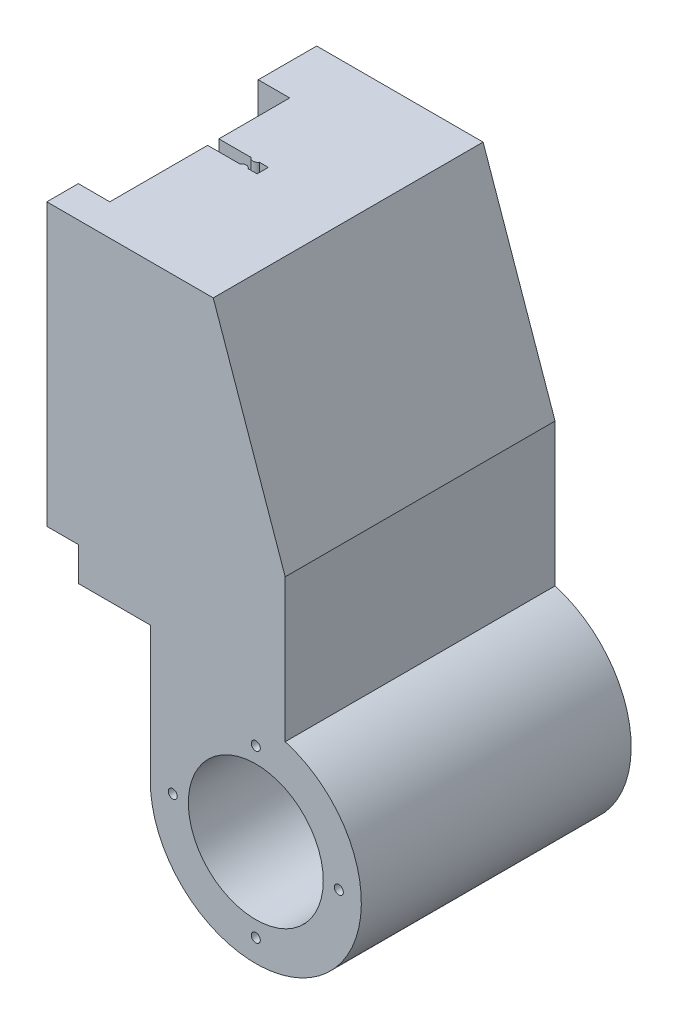
SolidWorks part; units mm, degrees
ref_plane "Front Plane" through (0, 0, 0) normal (0, 0, 1) x (1, 0, 0)
ref_plane "Top Plane" through (0, 0, 0) normal (0, 1, 0) x (1, 0, 0)
ref_plane "Right Plane" through (0, 0, 0) normal (1, 0, 0) x (0, 0, -1)
sketch "Sketch1" plane through (0, 0, 0.7555) normal (0, 0, 1) x (1, 0, 0)
  line L0 (-30.8511, 11.3225) -> (-30.8511, 7.8225)
  line L1 (-37.1011, 17.5725) -> (-40.6011, 17.5725)
  line L2 (-30.8511, 27.3225) -> (-30.8511, 23.8225)
  line L3 (-24.6011, 17.5725) -> (-21.1011, 17.5725)
  circle A2 centre (-30.8511, 9.5725) radius 0.75
  circle A3 centre (-38.8511, 17.5725) radius 0.75
  circle A4 centre (-30.8511, 25.5725) radius 0.75
  circle A5 centre (-22.8511, 17.5725) radius 0.75
  circle A6 centre (-30.8511, 17.5725) radius 16
  circle A7 centre (-30.8511, 17.5725) radius 5.3
  line M1 (-24.957, 26.8601) -> (-29.1868, 25.0317)
  line M2 (-29.1868, 25.0317) -> (-28.1663, 21.9086)
  line M3 (-28.1663, 21.9086) -> (-24.957, 26.8601)
  dimension "D1" = 32
  dimension "D2" = 10.6
  dimension "D3" = 1.5
  dimension "D4" = 1.5
  dimension "D5" = 1.5
  dimension "D6" = 1.5
extrude "Boss-Extrude1" add sketch "Sketch1" along normal blind 60 contours A6 A7 A2 A3 A4 A5 M2 M1 M3 | A7 M3 M1 M2 | A7 M2 M3 | L1 A3 | L1 A3 | L0 A2 | L0 A2 | L3 A5 | L3 A5 | L2 A4 | L2 A4 region at (-30.5328, 9.5725, 0.7555) region at (-31.1694, 9.5725, 0.7555) region at (-38.8511, 17.2542, 0.7555) region at (-38.8511, 17.8908, 0.7555) region at (-30.5328, 25.5725, 0.7555) region at (-31.1694, 25.5725, 0.7555) region at (-22.8511, 17.8908, 0.7555) region at (-22.8511, 17.2542, 0.7555) region at (-46.3986, 17.5725, 0.7555) region at (-30.8518, 17.5713, 0.7555) region at (-27.4344, 24.6082, 0.7555)
sketch "Sketch2" plane through (0, 0, 60.7555) normal (0, 0, 1) x (1, 0, 0)
  line L0 (-46.8511, 17.5725) -> (-46.8511, 117.5725)
  line L1 (-46.8511, 117.5725) -> (-14.8511, 117.5725)
  line L2 (-14.8511, 117.5725) -> (-14.8511, 17.5725)
  line L3 (-30.8511, 17.5725) -> (-60.8511, 17.5725)
  line L4 (-60.8511, 57.5725) -> (-60.8511, 117.5725)
  line L5 (-60.8511, 117.5725) -> (-46.8511, 117.5725)
  line L7 (-30.8511, 117.5725) -> (-14.8511, 71.8582)
  line L8 (-60.8511, 57.5725) -> (-60.8511, 17.5725)
  circle A0 centre (-30.8511, 17.5725) radius 16 construction
  circle M7 centre (-30.8511, 17.5725) radius 16
  dimension "D1" = 100
  dimension "D2" = 30
  dimension "D3" = 100
  dimension "D4" = 60
extrude "Boss-Extrude2" add sketch "Sketch2" against normal blind 60 contours L7 L1 L0 L2 M7 | L4 L0 L5 region at (-53.8511, 67.5725, 60.7555) region at (-32.455, 69.4896, 60.7555)
sketch "Sketch3" plane through (0, 117.5725, 0) normal (0, 1, 0) x (1, 0, 0)
  line L0 (-60.8511, -0.7555) -> (-60.8511, -28.7555)
  line L1 (-60.8511, -0.7555) -> (-60.8511, -60.7555) construction
  line L2 (-60.8511, -60.7555) -> (-60.8511, -32.7555)
  line L3 (-30.8511, -0.7555) -> (-30.8511, -29.5055)
  line L4 (-30.8511, -0.7555) -> (-30.8511, -60.7555) construction
  line L5 (-30.8511, -60.7555) -> (-30.8511, -32.0055)
  line L6 (-60.8511, -0.7555) -> (-49.8511, -0.7555)
  line L7 (-60.8511, -0.7555) -> (-30.8511, -0.7555) construction
  line L8 (-60.8511, -0.7555) -> (-58.8511, -0.7555)
  line L9 (-58.8511, -0.7555) -> (-58.8511, -60.7555)
  line L10 (-60.8511, -60.7555) -> (-30.8511, -60.7555) construction
  line L11 (-49.8511, -0.7555) -> (-49.8511, -60.7555)
  line L12 (-30.8511, -29.5055) -> (-58.8511, -29.5055)
  line L13 (-30.8511, -32.0055) -> (-58.8511, -32.0055)
  line L14 (-58.8511, -30.7555) -> (-60.8511, -30.7555)
  line L15 (-59.8511, -31.5055) -> (-59.8511, -30.0055)
  line L16 (-49.8511, -30.7555) -> (-53.8511, -30.7555)
  line L17 (-59.7707, -32.5947) -> (-49.8511, -32.5947)
  line L18 (-59.7707, -28.9162) -> (-49.8511, -28.9162)
  line L19 (-53.8511, -28.9162) -> (-53.8511, -32.5947)
  line L20 (-58.8511, -29.5055) -> (-60.8511, -29.5055)
  line L21 (-60.8511, -0.7555) -> (-60.8511, -60.7555) construction
  line L22 (-58.8511, -32.0055) -> (-60.8511, -32.0055)
  arc A0 (-60.8511, -28.7555) -> (-58.8511, -29.5055) centre (-59.7707, -28.9162) ccw
  arc A1 (-60.8511, -32.7555) -> (-58.8511, -32.0055) centre (-59.7707, -32.5947) cw
  circle A2 centre (-52.7589, -32.5947) radius 1.0922
  circle A3 centre (-52.7589, -28.9162) radius 1.0922
  point P31 (-59.8511, -30.7555)
  point P46 (-53.8511, -30.7555)
  line M10 (-60.8511, -0.7555) -> (-60.8511, -60.7555)
  dimension "D7" = 2.1845
  dimension "D8" = 2.1845
  dimension "D1" = 4
  dimension "D2" = 2.5
  dimension "D3" = 11
  dimension "D4" = 2
  dimension "D5" = 1.5
  dimension "D6" = 4
extrude "Cut-Extrude1" cut sketch "Sketch3" against normal through all contours L13 L11 L12 L9 | A3 L12 L19 L16 L11 | A2 L13 L11 L16 L19 | A0 L15 L14 L9 | A0 L20 L14 L15 M10 | L22 A1 L15 L14 M10 | L15 A1 L9 L14 | L20 A0 | A1 L22 region at (-60.4035, 117.5725, 30.2566) region at (-59.7707, 117.5725, 29.7112) region at (-56.3511, 117.5725, 30.7555) region at (-59.3076, 117.5725, 30.3023) region at (-60.4035, 117.5725, 31.2543) region at (-51.7149, 117.5725, 30.1933) region at (-59.3076, 117.5725, 31.2087) region at (-51.7149, 117.5725, 31.3176) region at (-59.7707, 117.5725, 31.7997)
sketch "Sketch4" plane through (0, 117.5725, 0) normal (0, 1, 0) x (1, 0, 0)
  line L0 (-60.8511, -27.2555) -> (-44.8511, -0.7555)
  line L1 (-60.8511, -0.7555) -> (-60.8511, -29.5055) construction
  line L2 (-60.8511, -0.7555) -> (-30.8511, -0.7555) construction
  line L3 (-60.8511, -34.2555) -> (-44.8511, -60.7555)
  line L4 (-60.8511, -32.0055) -> (-60.8511, -60.7555) construction
  line L5 (-60.8511, -60.7555) -> (-30.8511, -60.7555) construction
  line L6 (-44.8511, -0.7555) -> (-60.8511, -0.7555)
  line L7 (-60.8511, -0.7555) -> (-60.8511, -27.2555)
  line L8 (-60.8511, -34.2555) -> (-60.8511, -60.7555)
  line L9 (-60.8511, -60.7555) -> (-44.8511, -60.7555)
  dimension "D1" = 16
  dimension "D2" = 26.5
  dimension "D3" = 26.5
  dimension "D4" = 16
extrude "Cut-Extrude2" cut sketch "Sketch4" against normal through all
sketch "Sketch5" plane through (0, 0, 0.7555) normal (0, 0, -1) x (-1, 0, 0)
  line L0 (30.8511, 17.5725) -> (30.8511, 47.5725)
  line L1 (30.8511, 47.5725) -> (84.8511, 47.5725)
  line L3 (44.8511, 9.8265) -> (44.8511, 47.5725)
  line L4 (44.8511, 9.8265) -> (44.8511, 117.5725) construction
  line L5 (44.8511, 9.8265) -> (84.8511, 9.8265)
  line L6 (84.8511, 9.8265) -> (84.8511, 47.5725)
  line M8 (44.8511, 9.8265) -> (44.8511, 117.5725)
  dimension "D1" = 30
  dimension "D2" = 40
extrude "Cut-Extrude5" cut sketch "Sketch5" against normal through all contours L5 L6 L1 M8 region at (-64.8511, 28.6995, 0.7555)
sketch "Sketch10" plane through (0, 0, 60.7555) normal (0, 0, 1) x (1, 0, 0)
  line L0 (-44.8511, 9.8265) -> (-44.8511, 47.5725) construction
  line L1 (-21.3871, 17.5725) -> (-56.3871, 17.5725)
  line L2 (-21.3871, 17.5725) -> (-21.3871, -17.4275)
  line L3 (-30.8511, 17.5725) -> (-21.3871, 17.5725)
  line L4 (-24.6011, 17.5725) -> (-21.1011, 17.5725) construction
  line L5 (-21.3871, 17.5725) -> (-2.9231, 17.5725)
  line L6 (-2.9231, 17.5725) -> (-2.9231, 19.3225)
  line L7 (-21.3871, 17.5725) -> (-6.3871, 17.5725)
  circle A0 centre (-21.3871, 17.5725) radius 23.464
  circle A1 centre (-2.9231, 17.5725) radius 1
  circle A2 centre (-21.3871, -0.8915) radius 1
  circle A3 centre (-39.8511, 17.5725) radius 1
  circle A4 centre (-21.3871, 36.0365) radius 1
  circle A5 centre (-21.3871, 17.5725) radius 35
  circle A6 centre (-21.3871, 17.5725) radius 15
  point P21 (-21.3871, 17.5725)
  line M2 (-44.8511, 47.5725) -> (-44.8511, 9.8265)
  arc M3 (-44.8511, 9.8265) -> (-14.8511, 17.5725) centre (-30.8511, 17.5725) ccw
  line M4 (-14.8511, 17.5725) -> (-14.8511, 71.8582)
  arc M8 (-28.2602, 22.1961) -> (-28.0575, 22.0765) centre (-30.8511, 17.5725) cw
  line M9 (-28.0575, 22.0765) -> (-28.1663, 21.9086)
  line M10 (-28.1663, 21.9086) -> (-28.2602, 22.1961)
  dimension "D4" = 2
  dimension "D8" = 30
  dimension "D1" = 9.464
  dimension "D2" = 18.464
  dimension "D3" = 1.75
  dimension "D6" = 35
  dimension "D7" = 15
  dimension "D5" = 4
extrude "Boss-Extrude3" add sketch "Sketch10" against normal up to surface (60 mm away) contours A2 L2 A0 M3 | A3 L1 A0 L2 M3 | L5 L2 M3 | A2 L2 A0 A1 M4 M3 | A3 L1 L5 A0 A4 M4 M10 M8 M9 | L1 A3 | L1 A3 | A4 | L5 A1 L6 | L6 A1 L5 | L2 A2 | L2 A2 | L5 A6 M4 | L2 A6 L5 M3 | A6 L2 M3 | L1 A6 L2 M3 | A6 A0 L1 A3 A4 M4 region at (-27.8512, 11.3508, 60.7555) region at (-18.7207, 12.5689, 60.7555) region at (-24.4076, 24.2518, 60.7555) region at (-13.1664, 10.5233, 60.7555) region at (-22.4089, 3.3164, 60.7555) region at (-11.3674, 22.9008, 60.7555) region at (-37.3564, 9.1245, 60.7555) region at (-31.0311, 31.187, 60.7555) region at (-3.3475, 17.9969, 60.7555) region at (-2.7816, 17.431, 60.7555) region at (-10.4154, 6.6008, 60.7555) region at (-28.6623, -0.913, 60.7555) region at (-39.8511, 17.1481, 60.7555) region at (-39.8511, 17.9969, 60.7555) region at (-20.9627, -0.8915, 60.7555) region at (-21.8115, -0.8915, 60.7555) region at (-21.3871, 36.0365, 60.7555) up to face at (-28.1611, 22.0608, 0.7555)
extrude "Cut-Extrude6" cut sketch "Sketch10<4>" against normal up to surface (60 mm away) contours A0 M2 M3 | L1 A3 | L1 A3 | L2 A2 | L2 A2 | L6 A1 L5 | L5 A1 L6 | A4 region at (-3.3475, 17.9969, 60.7555) region at (-2.7816, 17.431, 60.7555) region at (-39.8511, 17.1481, 60.7555) region at (-39.8511, 17.9969, 60.7555) region at (-20.9627, -0.8915, 60.7555) region at (-21.8115, -0.8915, 60.7555) region at (-43.9655, 10.1498, 60.7555) region at (-21.3871, 36.0365, 60.7555) up to face at (-30.2267, 55.7636, 0.7555)
sketch "Sketch10<4>" plane through (0, 0, 60.7555) normal (0, 0, 1) x (1, 0, 0) same geometry as "Sketch10"
extrude "Cut-Extrude7" cut sketch "Sketch10<5>" against normal up to surface (60 mm away) contours L2 A6 L5 M3 | L5 A6 M4 | A6 L1 L5 M4 M10 M8 M9 | L5 L2 M3 | L1 A6 L2 M3 | A6 L2 M3 region at (-27.8512, 11.3508, 60.7555) region at (-18.7207, 12.5689, 60.7555) region at (-24.4076, 24.2518, 60.7555) region at (-13.1664, 10.5233, 60.7555) region at (-22.4089, 3.3164, 60.7555) region at (-11.3674, 22.9008, 60.7555) up to face at (-28.1611, 22.0608, 0.7555)
sketch "Sketch10<5>" plane through (0, 0, 60.7555) normal (0, 0, 1) x (1, 0, 0) same geometry as "Sketch10"
sketch "Sketch11" plane through (0, 117.5725, 0) normal (0, 1, 0) x (1, 0, 0)
  line L0 (-44.8511, -0.7555) -> (-60.8511, -0.7555)
  line L1 (-60.8511, -0.7555) -> (-60.8511, -27.2555)
  line L2 (-60.8511, -27.2555) -> (-44.8511, -0.7555)
  line L3 (-60.8511, -34.2555) -> (-60.8511, -60.7555)
  line L4 (-60.8511, -60.7555) -> (-44.8511, -60.7555)
  line L5 (-60.8511, -34.2555) -> (-44.8511, -60.7555) construction
  line L6 (-44.8511, -60.7555) -> (-30.8511, -60.7555) construction
  line L7 (-44.8511, -60.7555) -> (-60.8511, -34.2555)
extrude "Boss-Extrude4" add sketch "Sketch11" against normal up to surface (70 mm away) up to face at (-53.6537, 47.5725, 30.7555)
sketch "Sketch12" plane through (0, 117.5725, 0) normal (0, 1, 0) x (1, 0, 0)
  line L0 (-60.8511, -0.7555) -> (-67.8511, -0.7555)
  line L1 (-67.8511, -0.7555) -> (-67.8511, -13.7555)
  line L2 (-67.8511, -13.7555) -> (-60.8511, -13.7555)
  line L3 (-60.8511, -0.7555) -> (-60.8511, -27.2555) construction
  line L4 (-60.8511, -13.7555) -> (-60.8511, -0.7555)
  line L5 (-60.8511, -60.7555) -> (-67.8511, -60.7555)
  line L6 (-67.8511, -60.7555) -> (-67.8511, -53.7555)
  line L7 (-67.8511, -53.7555) -> (-60.8511, -53.7555)
  line L8 (-60.8511, -34.2555) -> (-60.8511, -60.7555) construction
  line L9 (-60.8511, -53.7555) -> (-60.8511, -60.7555)
  line L10 (-60.8511, -29.5055) -> (-60.8511, -32.0055)
  point P18 (-60.8511, -30.7555)
  line M8 (-60.8511, -0.7555) -> (-60.8511, -29.5055)
  line M16 (-60.8511, -32.0055) -> (-60.8511, -60.7555)
  dimension "D1" = 23
  dimension "D2" = 17
  dimension "D3" = 7
  dimension "D4" = 7
extrude "Boss-Extrude5" add sketch "Sketch12" against normal blind 62.5 contours L1 L2 L0 M8 | L7 L6 L5 M16 region at (-64.3511, 117.5725, 7.2555) region at (-64.3511, 117.5725, 57.2555)
sketch "Sketch13" plane through (0, 47.5725, 0) normal (0, -1, 0) x (1, 0, 0)
  line L0 (-60.8511, 32.0055) -> (-49.8511, 32.0055)
  line L1 (-49.8511, 32.0055) -> (-49.8511, 29.5055)
  line L2 (-49.8511, 29.5055) -> (-60.8511, 29.5055)
  line L3 (-60.8511, 29.5055) -> (-60.8511, 32.0055)
extrude "Cut-Extrude8" cut sketch "Sketch13" against normal blind 40
